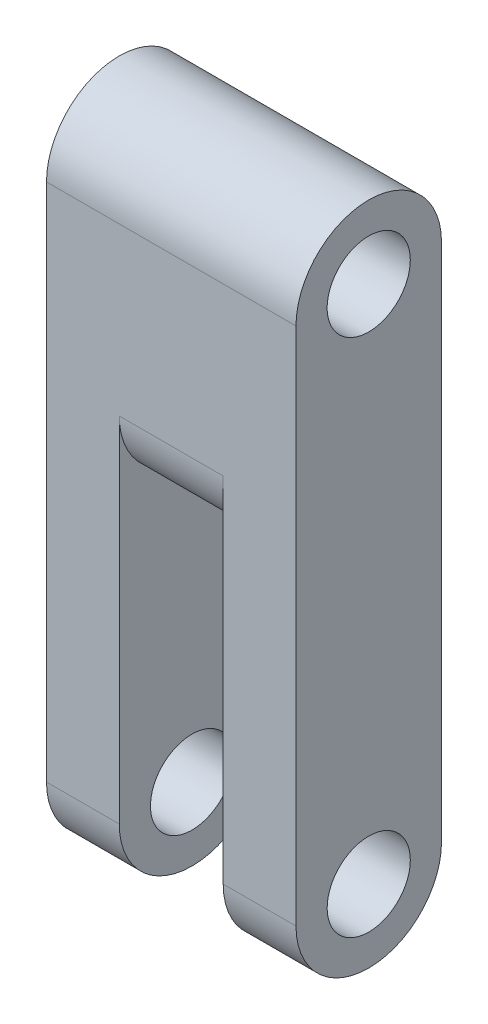
SolidWorks part; units mm, degrees
material "ABS"
ref_plane "Спереди" through (0, 0, 0) normal (0, 0, 1) x (1, 0, 0)
ref_plane "Сверху" through (0, 0, 0) normal (0, 1, 0) x (1, 0, 0)
ref_plane "Справа" through (0, 0, 0) normal (1, 0, 0) x (0, 0, -1)
sketch "Эскиз1" plane through (0, 0, 0) normal (1, 0, 0) x (0, 0, -1)
  line L0 (3.5, 30) -> (3.5, -49970) construction
  line L2 (0, 0) -> (0, 25)
  line L4 (7, 0) -> (7, 25)
  line L5 (0, 0) -> (7, 25) construction
  line L6 (0, 25) -> (7, 0) construction
  line L7 (3.5, 12.5) -> (50003.5, 12.5) construction
  circle A0 centre (3.5, 25) radius 2
  arc A1 (0, 25) -> (7, 25) centre (3.5, 25) cw
  circle A2 centre (3.5, 0) radius 2
  arc A3 (0, 0) -> (7, 0) centre (3.5, 0) ccw
  point P4 (3.5, 12.5)
  dimension "D3" = 4
  dimension "D4" = 3.5
  dimension "D1" = 25
  dimension "D2" = 7
  dimension "D5" = 25
extrude "Бобышка-Вытянуть1" add sketch "Эскиз1" along normal blind 12 contours L2 A1 L4 A3
sketch "Эскиз2" plane through (12, 0, 0) normal (1, 0, 0) x (0, 0, -1)
  line L0 (0, 11.9718) -> (0, 50011.9718) construction
  line L2 (7, 19.5747) -> (7, -49980.4253) construction
  line L4 (3.5, 33.5) -> (3.5, -49966.5) construction
  line L5 (0, 0) -> (50000, 0) construction
  line L6 (0, 25) -> (50000, 25) construction
  line L7 (-2.9994, 12.5) -> (49997.0006, 12.5) construction
  arc A0 (7, 25) -> (0, 25) centre (3.5, 25) ccw construction
  arc A1 (0, 0) -> (7, 0) centre (3.5, 0) ccw construction
  circle A2 centre (3.5, 25) radius 2
  circle A3 centre (3.5, 0) radius 2
  point P9 (3.5, 28.5)
  point P13 (3.5, -3.5)
  point P22 (3.5, 25)
  dimension "D3" = 4
  dimension "D1" = 25
  dimension "D2" = 12.5
extrude "Вырез-Вытянуть2" cut sketch "Эскиз2" against normal blind 15
ref_plane "Плоскость1" through (3.5, 0, 0) normal (1, 0, 0) x (0, 0, -1)
sketch "Эскиз3" plane through (3.5, 0, 0) normal (1, 0, 0) x (0, 0, -1)
  line L0 (0, 0) -> (50000, 0) construction
  line L1 (-996.5, 25) -> (49003.5, 25) construction
  line L3 (-1005.198, 17) -> (48994.802, 17) construction
  line L4 (-14.8525, 21) -> (12.3896, 21) construction
  line L8 (-5.9735, 17) -> (-5.9735, -6.2075)
  line L9 (-5.9735, -6.2075) -> (11.9268, -6.2075)
  line L10 (11.9268, -6.2075) -> (11.9268, 17)
  line L12 (7, 17) -> (11.9268, 17)
  line L13 (0, 17) -> (-5.9735, 17)
  arc A3 (0, 17) -> (7, 17) centre (3.5, 17) ccw
  dimension "D4" = 23.2075
  dimension "D5" = 17.9003
  dimension "D3" = 3.5
  dimension "D1" = 8
  dimension "D2" = 4
  dimension "D6" = 8.4268
extrude "Вырез-Вытянуть3" cut sketch "Эскиз3" along normal blind 5
